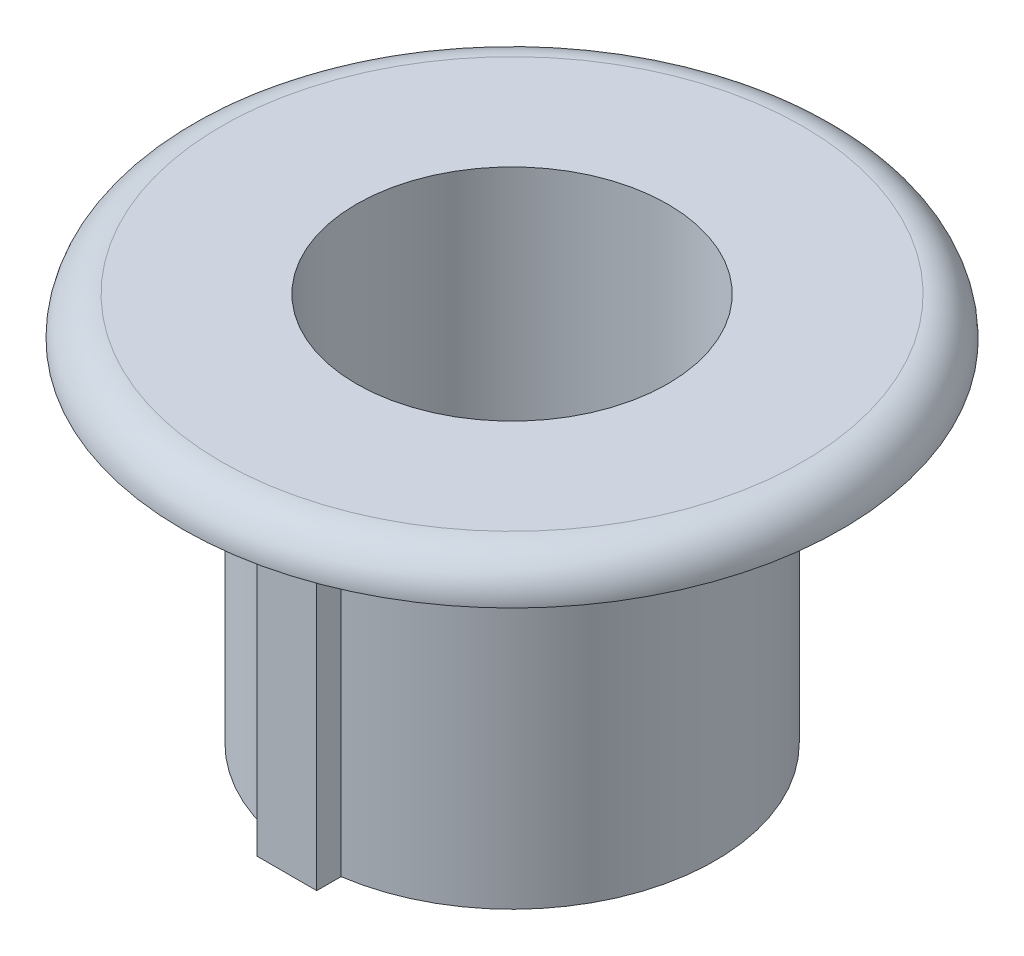
SolidWorks part; units mm, degrees
ref_plane "Plane1" through (0, 0, 0) normal (0, 0, 1) x (1, 0, 0)
ref_plane "Plane2" through (0, 0, 0) normal (0, 1, 0) x (1, 0, 0)
ref_plane "Plane3" through (0, 0, 0) normal (1, 0, 0) x (0, 0, -1)
sketch "Sketch1" plane through (0, 0, 0) normal (0, 0, 1) x (1, 0, 0)
  line L2 (10.414, 39.3863) -> (9.6266, 39.3863)
  line L3 (9.6266, 39.3863) -> (9.6266, 40.9103)
  line L4 (9.6266, 40.9103) -> (7.9502, 40.9103)
  line L5 (7.9502, 40.9103) -> (7.9502, 27.1943)
  line L6 (7.9502, 27.1943) -> (6.096, 27.1943)
  line L7 (6.096, 27.1943) -> (6.096, 42.4343)
  line L8 (6.096, 42.4343) -> (12.9032, 42.4343)
  line L9 (12.9032, 42.4343) -> (12.9032, 40.9103)
  line L10 (12.9032, 40.9103) -> (10.414, 40.9103)
  line L11 (10.414, 40.9103) -> (10.414, 39.3863)
  line L13 (0, 42.4343) -> (0, 27.1943) construction
  dimension "D1" = 1.524
  dimension "D2" = 6.096
  dimension "D3" = 12.9032
  dimension "D4" = 15.24
  dimension "D5" = 3.048
  dimension "D6" = 0.7874
  dimension "D7" = 7.9502
  dimension "D8" = 4.318
revolve "Base-Revolve" add sketch "Sketch1" angle 360 about L13
fillet "Fillet1" radius 1.524 1 edges at (0, 42.4343, 12.9032)
sketch "Sketch3" plane through (0, 27.1943, 0) normal (0, -1, 0) x (1, 0, 0)
  line L0 (-1.1665, 7.8642) -> (-1.1665, 8.8138)
  line L1 (-1.1665, 8.8138) -> (1.1665, 8.8138)
  line L2 (1.1665, 8.8138) -> (1.1665, 7.8642)
  line L3 (0, 8.8138) -> (0, 0) construction
  circle A0 centre (0, 0) radius 7.9502 construction
  arc A1 (1.1665, 7.8642) -> (-1.1665, 7.8642) centre (0, 0) ccw
  dimension "D1" = 2.3331
  dimension "D2" = 16.764
extrude "Boss-Extrude1" add sketch "Sketch3" along normal up to surface (-13.716 mm away) up to face at (0, 40.9103, 7.9502)
